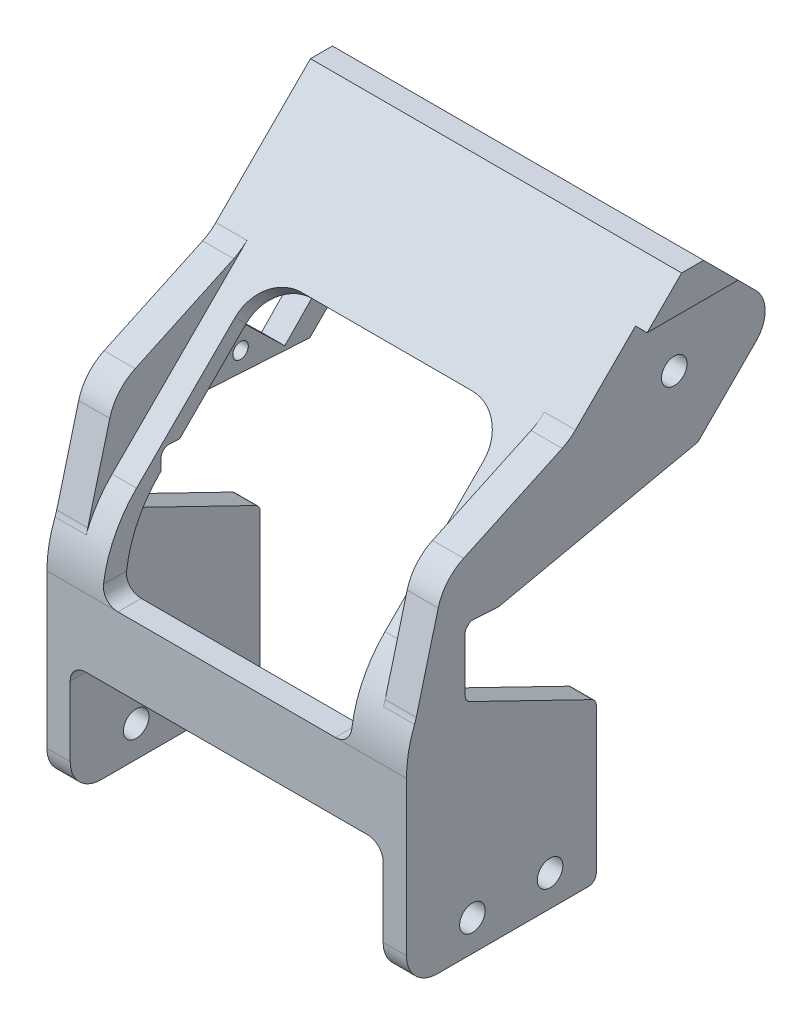
SolidWorks part; units mm, degrees
ref_plane "前视基准面" through (0, 0, 0) normal (0, 0, 1) x (1, 0, 0)
ref_plane "上视基准面" through (0, 0, 0) normal (0, 1, 0) x (1, 0, 0)
ref_plane "右视基准面" through (0, 0, 0) normal (1, 0, 0) x (0, 0, -1)
other "Configuration Table"
sketch "草图1" plane through (0, 0, 0) normal (0, 0, 1) x (1, 0, 0)
  line L1 (-23.15, 15) -> (23.15, 15)
  line L2 (-23.15, 15) -> (-23.15, -15)
  line L3 (-23.15, -15) -> (23.15, -15)
  line L4 (23.15, 15) -> (23.15, -15)
  line L5 (-23.15, 15) -> (23.15, -15) construction
  line L6 (-23.15, -15) -> (23.15, 15) construction
  point P0 (0, 0)
  dimension "D1" = 46.3
  dimension "D2" = 30
extrude "凸台-拉伸1" add sketch "草图1" along normal blind 27
sketch "草图2" plane through (0, 0, 0) normal (0, 0, -1) x (-1, 0, 0)
  line L0 (0, 15) -> (0, -15) construction
  line L1 (-23.15, 15) -> (23.15, 15) construction
  line L2 (23.15, -15) -> (-23.15, -15) construction
  line L3 (-23.15, -15) -> (-23.15, 15) construction
  line L4 (20.15, 0) -> (-20.15, 0)
  line L5 (20.15, 0) -> (20.15, -15)
  line L6 (20.15, -15) -> (-20.15, -15)
  line L7 (-20.15, 0) -> (-20.15, -15)
  line L8 (20.15, 0) -> (-20.15, -15) construction
  line L9 (20.15, -15) -> (-20.15, 0) construction
  point P6 (0, -7.5)
  dimension "D1" = 3
  dimension "D2" = 15
extrude "切除-拉伸1" cut sketch "草图2" against normal through all both and the other way through all
sketch "草图3" plane through (-23.15, 0, 0) normal (-1, 0, 0) x (0, 0, 1)
  line L0 (2, 15) -> (-20.8553, 37.8553)
  line L1 (-20.8553, 37.8553) -> (-8.3553, 50.3553)
  line L2 (-8.3553, 50.3553) -> (27, 15)
  line L3 (27, 15) -> (0, 15) construction
  line L4 (2, 15) -> (27, 15)
  dimension "D1" = 45
  dimension "D2" = 50
  dimension "D3" = 25
extrude "凸台-拉伸2" add sketch "草图3" against normal up to surface (46.3 mm away) up to face at (23.15, 0, 13.5)
sketch "草图4" plane through (0, 8.5, 8.5) normal (0, -0.7071, -0.7071) x (1, 0, 0)
  line L0 (0, -12.0208) -> (0, -41.5147) construction
  line L1 (23.15, -12.0208) -> (-23.15, -12.0208) construction
  line L2 (23.15, -41.5147) -> (-23.15, -41.5147) construction
  line L3 (-23.15, -41.5147) -> (-23.15, -9.1924) construction
  line L4 (20.15, -18.0208) -> (-20.15, -18.0208)
  line L5 (20.15, -18.0208) -> (20.15, -41.5147)
  line L6 (20.15, -41.5147) -> (-20.15, -41.5147)
  line L7 (-20.15, -18.0208) -> (-20.15, -41.5147)
  line L8 (20.15, -18.0208) -> (-20.15, -41.5147) construction
  line L9 (20.15, -41.5147) -> (-20.15, -18.0208) construction
  point P6 (0, -29.7678)
  dimension "D1" = 3
  dimension "D2" = 6
extrude "切除-拉伸2" cut sketch "草图4" against normal through all both and the other way through all
sketch "草图5" plane through (-23.15, 0, 0) normal (-1, 0, 0) x (0, 0, 1)
  line L0 (13.5, 0) -> (13.5, -15) construction
  line L4 (0, -15) -> (27, -15)
  line L5 (27, -15) -> (27, 0)
  line L6 (27, 0) -> (0, 0)
  line L7 (0, 0) -> (0, -15)
  line L8 (0, -15) -> (27, -15) construction
  line L9 (27, -15) -> (27, 0) construction
  line L10 (27, 0) -> (0, 0) construction
  line L11 (0, 0) -> (0, -15) construction
  circle A0 centre (18.5, -11) radius 1.65
  circle A1 centre (8.5, -11) radius 1.65
  dimension "D2" = 3.3
  dimension "D3" = 10
  dimension "D4" = 4
  dimension "D1" = 0
extrude "切除-拉伸3" cut sketch "草图5" against normal through all both and the other way through all
sketch "草图6" plane through (-23.15, 0, 0) normal (-1, 0, 0) x (0, 0, 1)
  line L0 (-14.6053, 44.1053) -> (27, 2.5) construction
  line L1 (-8.3553, 50.3553) -> (-20.8553, 37.8553) construction
  line L2 (27, 15) -> (27, -15) construction
  line L3 (27, 15) -> (-8.3553, 50.3553) construction
  line L4 (10.6737, 26.958) -> (-10.5395, 48.1712) construction
  line L5 (10.6737, 26.958) -> (2.542, 18.8263) construction
  line L6 (-10.5395, 48.1712) -> (-18.6712, 40.0395) construction
  line L7 (2.542, 18.8263) -> (-18.6712, 40.0395) construction
  line L8 (10.6737, 26.958) -> (-18.6712, 40.0395) construction
  line L9 (-10.5395, 48.1712) -> (2.542, 18.8263) construction
  line L10 (7.8281, 29.7913) -> (-7.3616, 45.4282)
  line L11 (7.8281, 29.7913) -> (-0.6358, 21.5693)
  line L12 (-7.3616, 45.4282) -> (-15.8256, 37.2062)
  line L13 (-0.6358, 21.5693) -> (-15.8256, 37.2062)
  line L14 (7.8281, 29.7913) -> (-15.8256, 37.2062) construction
  line L15 (-7.3616, 45.4282) -> (-0.6358, 21.5693) construction
  line L16 (0.2333, 37.6097) -> (-8.2307, 29.3877) construction
  circle A0 centre (-13.3335, 42.8335) radius 1
  circle A2 centre (5.0614, 23.8972) radius 1
  point P9 (-3.9987, 33.4987)
  point P15 (-3.9987, 33.4987)
  dimension "D6" = 2
  dimension "D1" = 11.5
  dimension "D2" = 30
  dimension "D3" = 21.8
  dimension "D4" = 11.8
  dimension "D5" = 13.2
extrude "切除-拉伸5" cut sketch "草图6" against normal blind 12.4
sketch "草图8" plane through (20.15, 0, 0) normal (-1, 0, 0) x (0, 0, 1)
  line L0 (-8.3553, 50.3553) -> (-20.8553, 37.8553) construction
  line L1 (-14.6053, 44.1053) -> (2.0074, 27.4926) construction
  line L2 (8.2574, 33.7426) -> (-4.2426, 21.2426) construction
  line L3 (8.2574, 33.7426) -> (-8.3553, 50.3553) construction
  circle A0 centre (-7.4989, 36.9989) radius 1.65
  dimension "D2" = 3.3
  dimension "D1" = 10.05
extrude "切除-拉伸7" cut sketch "草图8" against normal blind 10
fillet "圆角1" radius 4 4 edges at (21.65, -15, 27) (-21.65, -15, 27) (21.65, 37.8553, -20.8553) (-21.65, 37.8553, -20.8553)
sketch "草图9" plane through (0, 21, 21) normal (0, 0.7071, 0.7071) x (1, 0, 0)
  line L1 (-20.15, 41.5147) -> (20.15, 41.5147)
  line L2 (-20.15, 41.5147) -> (-20.15, 18.0208)
  line L3 (-20.15, 18.0208) -> (20.15, 18.0208)
  line L4 (20.15, 41.5147) -> (20.15, 18.0208)
extrude "凸台-拉伸4" add sketch "草图9" against normal blind 2
sketch "草图10" plane through (0, 21, 21) normal (0, 0.7071, 0.7071) x (1, 0, 0)
  line L0 (0, 41.5147) -> (0, -8.4853) construction
  line L1 (23.15, 41.5147) -> (-23.15, 41.5147) construction
  line L2 (23.15, -8.4853) -> (-23.15, -8.4853) construction
  line L4 (16, 20.6807) -> (-16, 20.6807)
  line L5 (16, 20.6807) -> (16, -19.3193)
  line L6 (16, -19.3193) -> (-16, -19.3193)
  line L7 (-16, 20.6807) -> (-16, -19.3193)
  line L8 (16, 20.6807) -> (-16, -19.3193) construction
  line L9 (16, -19.3193) -> (-16, 20.6807) construction
  point P6 (0, 0.6807)
  dimension "D1" = 32
  dimension "D2" = 40
extrude "切除-拉伸8" cut sketch "草图10" against normal through all
sketch "草图11" plane through (-16, 0, 0) normal (1, 0, 0) x (0, 0, -1)
  line L0 (-6.8431, 32.3284) -> (-24, 15.1716)
  line L1 (-24, 15.1716) -> (-24, 0)
  line L2 (-27, -11) -> (-27, 15) construction
  line L3 (8.3553, 50.3553) -> (-27, 15) construction
  line L4 (-27, 15) -> (-27, 0) construction
  line L8 (-27, 15) -> (-27, 0)
  line L9 (-27, 0) -> (0, 0)
  line L10 (0, 0) -> (0, 15)
  line L11 (-2, 15) -> (4.2426, 21.2426)
  line L12 (-6.0926, 31.5779) -> (-6.8431, 32.3284)
  line L13 (-6.8431, 32.3284) -> (-4.9623, 34.2092)
  line L14 (-4.9623, 34.2092) -> (-6.3766, 35.6234)
  line L15 (-6.3766, 35.6234) -> (-27, 15)
  line L17 (-24, 0) -> (0, 0)
  line L18 (0, 0) -> (0, 15)
  line L20 (-6.0926, 31.5779) -> (-6.8431, 32.3284)
  line L25 (-2, 15) -> (4.2426, 21.2426)
  line L34 (0, 15) -> (-2, 15)
  line L35 (0, 15) -> (-2, 15)
  line L36 (4.2426, 21.2426) -> (2.2521, 23.2332)
  line L37 (4.2426, 21.2426) -> (2.2521, 23.2332)
  line L38 (2.2521, 23.2332) -> (0.6358, 21.5693)
  line L40 (2.2521, 23.2332) -> (0.6358, 21.5693)
  line L42 (0.6358, 21.5693) -> (-7.8281, 29.7913)
  line L44 (0.6358, 21.5693) -> (-7.8281, 29.7913)
  line L45 (-7.8281, 29.7913) -> (-6.0926, 31.5779)
  line L46 (-7.8281, 29.7913) -> (-6.0926, 31.5779)
  dimension "D2" = 3
  dimension "D1" = 0
extrude "切除-拉伸9" cut sketch "草图11" against normal up to surface (4.15 mm away) up to face at (-20.15, -12.65, 18.5)
sketch "草图12" plane through (16, 0, 0) normal (-1, 0, 0) x (0, 0, 1)
  line L0 (6.0926, 31.5779) -> (-2.2521, 23.2332)
  line L6 (24, 15.1716) -> (6.8431, 32.3284)
  line L7 (24, 0) -> (24, 15.1716)
  line L8 (0, 0) -> (24, 0)
  line L9 (0, 15) -> (0, 0)
  line L10 (-4.2426, 21.2426) -> (2, 15)
  line L11 (6.8431, 32.3284) -> (6.0926, 31.5779)
  line L12 (24, 15.1716) -> (6.8431, 32.3284)
  line L13 (24, 0) -> (24, 15.1716)
  line L14 (0, 0) -> (24, 0)
  line L15 (0, 15) -> (0, 0)
  line L17 (6.8431, 32.3284) -> (6.0926, 31.5779)
  line L18 (-4.2426, 21.2426) -> (2, 15)
  line L24 (2, 15) -> (0, 15)
  line L25 (2, 15) -> (0, 15)
  line L26 (-2.2521, 23.2332) -> (-4.2426, 21.2426)
  line L27 (-2.2521, 23.2332) -> (-4.2426, 21.2426)
  line L28 (-0.6358, 21.5693) -> (-2.2521, 23.2332)
  line L32 (7.8281, 29.7913) -> (-0.6358, 21.5693)
  line L35 (6.0926, 31.5779) -> (7.8281, 29.7913)
  dimension "D1" = 0
extrude "切除-拉伸10" cut sketch "草图12" against normal up to surface (4.15 mm away) up to face at (20.15, -9.35, 18.5)
fillet "圆角2" radius 15 4 edges at (18.075, 15.1716, 24) (-18.075, 15.1716, 24) (19.575, 15, 27) (-19.575, 15, 27)
fillet "圆角3" radius 5 2 edges at (-16, 34.9163, 5.6695) (16, 34.9163, 5.6695)
sketch "草图13" plane through (0, 0, 27) normal (0, 0, 1) x (1, 0, 0)
  line L0 (-16, 8.7868) -> (-23.15, 8.7868) construction
  line L1 (-20.15, 8.7868) -> (20.15, 8.7868)
  line L2 (-20.15, 8.7868) -> (-20.15, 0)
  line L3 (-20.15, 0) -> (20.15, 0)
  line L4 (20.15, 8.7868) -> (20.15, 0)
  line L5 (-20.15, -11) -> (-20.15, 0) construction
extrude "凸台-拉伸5" add sketch "草图13" against normal up to surface (3 mm away) up to face at (-18.075, 4.4792, 24)
fillet "圆角4" radius 2 4 edges at (-20.15, 0, 25.5) (20.15, 0, 25.5) (16, 8.7868, 25.5) (-16, 8.7868, 25.5)
sketch "草图14" plane through (-23.15, 0, 0) normal (-1, 0, 0) x (0, 0, 1)
  line L0 (23, -15) -> (0, -15) construction
  line L1 (0, 15) -> (2, 15)
  line L2 (0, 15) -> (0, -15)
  line L3 (0, -15) -> (2, -15)
  line L4 (2, 15) -> (2, -15)
extrude "切除-拉伸11" cut sketch "草图14" against normal through all
sketch "草图15" plane through (20.15, 0, 0) normal (-1, 0, 0) x (0, 0, 1)
  line L0 (-8.3553, 50.3553) -> (-14.2102, 44.5005)
  line L1 (-8.3553, 50.3553) -> (-18.0269, 40.6838) construction
  line L2 (-14.2102, 44.5005) -> (-2.5005, 44.5005)
  line L3 (-2.5005, 44.5005) -> (-8.3553, 50.3553)
  line L4 (22.6066, 19.3934) -> (-8.3553, 50.3553) construction
  dimension "D1" = 8.28
extrude "凸台-拉伸6" add sketch "草图15" against normal blind 4.5
chamfer "倒角2" distance 2 angle 45 1 edges at (0.75, 50.3553, -8.3553)
sketch "草图19" plane through (23.15, 0, 0) normal (1, 0, 0) x (0, 0, -1)
  line L0 (3.849, 20.849) -> (-19.4332, 22.2521)
  line L2 (-23, -15) -> (-2, -15) construction
  line L3 (-2.5483, -15) -> (3.849, -15)
  line L4 (3.849, -15) -> (3.849, 20.849)
  line L5 (-2, 15) -> (18.0269, 35.0269) construction
  line L6 (-19.4332, 22.2521) -> (-19.4332, 13.5697)
  line L8 (-19.4332, 13.5697) -> (-2.5483, 5.3581)
  line L9 (-2.5483, 5.3581) -> (-2.5483, -15)
extrude "切除-拉伸12" cut sketch "草图19" against normal through all
fillet "圆角5" radius 1 8 edges at (-21.65, 5.3581, 2.5483) (21.65, 5.3581, 2.5483) (-21.65, 13.5697, 19.4332) (-19.575, 22.2521, 19.4332) (21.65, 13.5697, 19.4332) (19.575, 22.2521, 19.4332) (-21.65, -15, 2.5483) (21.65, -15, 2.5483)
sketch "草图23" plane through (23.15, 0, 0) normal (1, 0, 0) x (0, 0, -1)
  line L0 (-15.1167, 21.9919) -> (10.5266, 27.5266)
  line L1 (3.849, 20.849) -> (-18.373, 22.1882) construction
  line L2 (3.849, 20.849) -> (18.0269, 35.0269) construction
  line L3 (10.5266, 27.5266) -> (3.849, 20.849)
  line L4 (3.849, 20.849) -> (-15.1167, 21.9919)
extrude "切除-拉伸15" cut sketch "草图23" against normal blind 10
sketch "草图25" plane through (23.15, 0, 0) normal (1, 0, 0) x (0, 0, -1)
  line L0 (-25.8338, 14.5856) -> (-22.1914, 28.4673)
  line L1 (-22.1914, 28.4673) -> (-5.984, 36.016)
  line L2 (2.5005, 44.5005) -> (-22.6066, 19.3934) construction
  line L3 (-5.984, 36.016) -> (-25.8338, 14.5856)
  arc A0 (-22.6066, 19.3934) -> (-27, 8.7868) centre (-12, 8.7868) ccw construction
extrude "凸台-拉伸7" add sketch "草图25" against normal blind 4
mirror "镜向1" about plane through (0, 0, 0) normal (1, 0, 0) of "凸台-拉伸7"
fillet "圆角6" radius 6 6 edges at (21.15, 14.5856, 25.8338) (-21.15, 14.5856, 25.8338) (-21.15, 28.4673, 22.1914) (21.15, 28.4673, 22.1914) (21.15, 36.016, 5.984) (-21.15, 36.016, 5.984)
